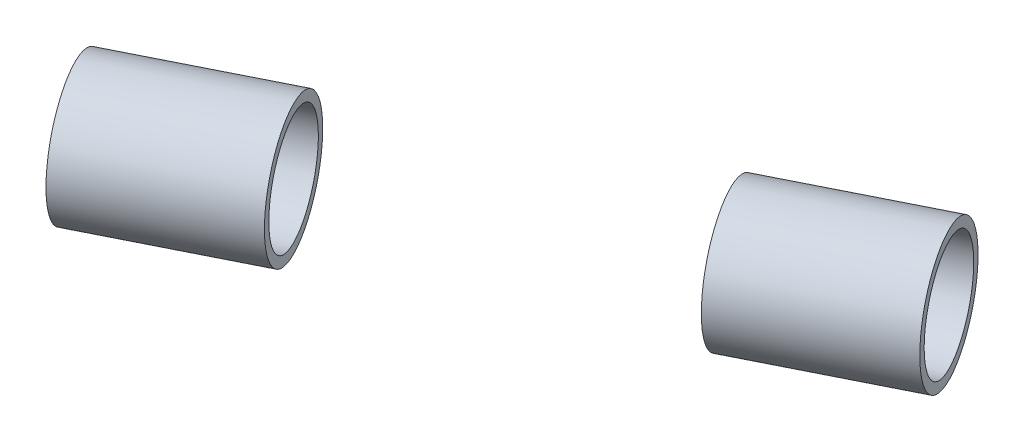
SolidWorks part; units mm, degrees
ref_plane "Płaszczyzna przednia" through (0, 0, 0) normal (0, 0, 1) x (1, 0, 0)
ref_plane "Płaszczyzna górna" through (0, 0, 0) normal (0, 1, 0) x (1, 0, 0)
ref_plane "Płaszczyzna prawa" through (0, 0, 0) normal (1, 0, 0) x (0, 0, -1)
sketch "Szkic2" plane through (0, 0, 0) normal (0, 1, 0) x (1, 0, 0)
  line L0 (0, -167.7051) -> (0, 0) construction
  line L1 (0, 0) -> (134.1641, -100.6231) construction
  line L2 (0, -167.7051) -> (134.1641, -100.6231) construction
  line L7 (13.4164, -138.6362) -> (-31.305, -160.9969)
  line L8 (0, -167.7051) -> (-8.9443, -149.8166) construction
  line L9 (13.4164, -138.6362) -> (22.3607, -156.5248)
  line L11 (22.3607, -156.5248) -> (-22.3607, -178.8854)
  line L13 (-22.3607, -178.8854) -> (-31.305, -160.9969)
  point P6 (0, 0)
  dimension "D1" = 150
  dimension "D2" = 150
  dimension "D3" = 40
  dimension "D4" = 50
revolve "Obrót1" add sketch "Szkic2" angle 360 about L2
sketch "Szkic3" plane through (0, 0, 0) normal (0, 1, 0) x (1, 0, 0)
  line L0 (111.8034, -111.8034) -> (102.8591, -93.9149)
  line L1 (0, -167.7051) -> (134.1641, -100.6231) construction
  line L2 (102.8591, -93.9149) -> (147.5805, -71.5542)
  line L3 (147.5805, -71.5542) -> (156.5248, -89.4427)
  line L4 (156.5248, -89.4427) -> (111.8034, -111.8034)
  line L5 (13.4164, -138.6362) -> (-31.305, -160.9969) construction
  point P4 (0, 0)
revolve "Obrót2" add sketch "Szkic3" angle 360 about L2
sketch "Szkic4" plane through (-89.4427, 0, 44.7214) normal (-0.8944, 0, 0.4472) x (0.4472, 0, 0.8944)
  circle A0 centre (150, 0) radius 17
  circle A1 centre (150, 0) radius 20 construction
  dimension "D1" = 3
extrude "Wytnij-wyciągnięcie1" cut sketch "Szkic4" against normal through all
sketch "Szkic5" plane through (0, 0, 0) normal (0, 1, 0) x (1, 0, 0)
  line L0 (13.4164, -138.6362) -> (13.4164, -116.2755)
  line L1 (13.4164, -116.2755) -> (84.9706, -80.4984)
  line L2 (84.9706, -80.4984) -> (102.8591, -93.9149)
  line L3 (0, 0) -> (134.1641, -100.6231) construction
  line L4 (13.4164, -138.6362) -> (-31.305, -160.9969) construction
  line L5 (13.4164, -138.6362) -> (-31.305, -160.9969)
  line L6 (-31.305, -160.9969) -> (-35.7771, -152.0526)
  line L7 (-35.7771, -152.0526) -> (-35.7771, -54.6139)
  line L9 (-35.7771, -54.6139) -> (65.1573, -4.1466)
  line L10 (65.1573, -4.1466) -> (143.1084, -62.6099)
  line L11 (143.1084, -62.6099) -> (147.5805, -71.5542)
  line L12 (147.5805, -71.5542) -> (102.8591, -93.9149)
  point P7 (-35.7771, -54.6139)
  point P17 (0, 0)
  point P21 (73.6356, -4.6581)
  point P22 (-35.7771, -37.5497)
  dimension "D1" = 20
  dimension "D2" = 10
